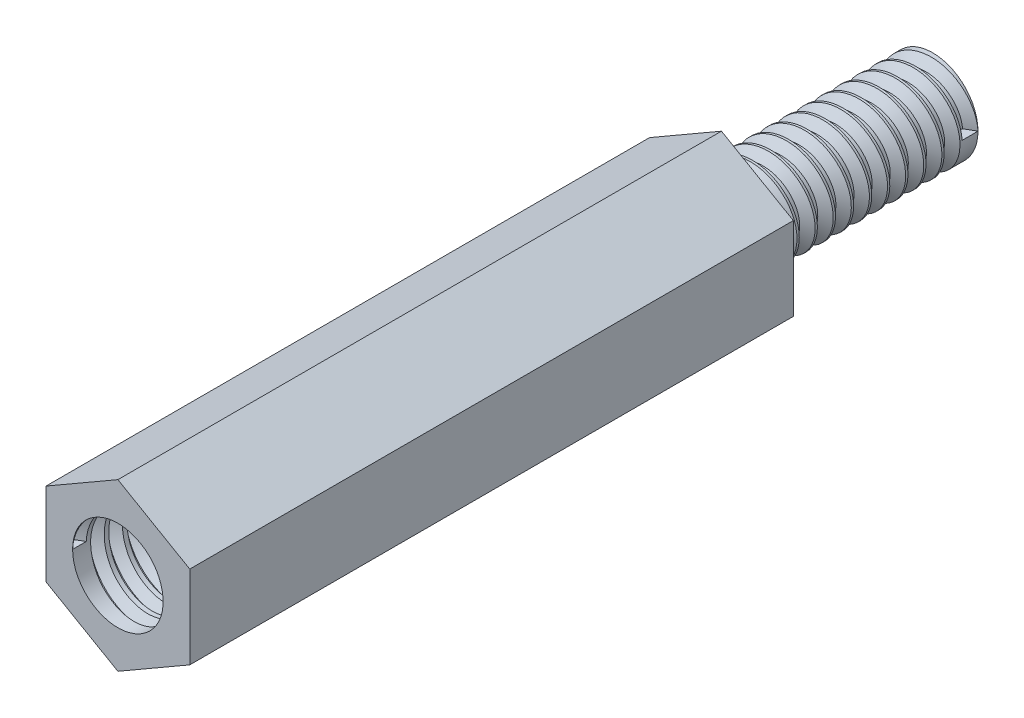
SolidWorks part; units mm, degrees
ref_plane "Front Plane" through (0, 0, 0) normal (0, 0, 1) x (1, 0, 0)
ref_plane "Top Plane" through (0, 0, 0) normal (0, 1, 0) x (1, 0, 0)
ref_plane "Right Plane" through (0, 0, 0) normal (1, 0, 0) x (0, 0, -1)
sketch "Sketch1" plane through (0, 0, 0) normal (0, 0, 1) x (1, 0, 0)
  line L1 (-2.3816, -1.375) -> (0, -2.75)
  line L2 (0, -2.75) -> (2.3816, -1.375)
  line L3 (2.3816, -1.375) -> (2.3816, 1.375)
  line L4 (2.3816, 1.375) -> (0, 2.75)
  line L5 (0, 2.75) -> (-2.3816, 1.375)
  line L6 (-2.3816, 1.375) -> (-2.3816, -1.375)
  circle A0 centre (0, 0) radius 2.3816 construction
  dimension "D1" = 5.5
extrude "Boss-Extrude1" add sketch "Sketch1" along normal blind 20
sketch "Sketch2" plane through (0, 0, 20) normal (0, 0, 1) x (1, 0, 0)
  circle A0 centre (0, 0) radius 1.5
  dimension "D1" = 3
extrude "Cut-Extrude1" cut sketch "Sketch2" against normal blind 7
sketch "Sketch3" plane through (0, 0, 0) normal (0, 0, -1) x (-1, 0, 0)
  circle A0 centre (0, 0) radius 1.5
  dimension "D1" = 3
extrude "Boss-Extrude2" add sketch "Sketch3" along normal blind 7
thread "Thread1" pitch 0.6 method cut profile "Thread Profile1" start angle 0, offset 0, length 0, pitch 0.6, diameter 3
ref_plane "Plane1" through (1.5, 0, -7) normal (0, -1, 0) x (1, 0, 0)
sketch "Thread Profile1" plane through (1.5, 0, -7) normal (0, -1, 0) x (1, 0, 0)
  line L0 (0, 0) -> (0, 0.6) construction
  line L11 (0, 0) -> (0, 0.525)
  line L12 (0, 0.525) -> (-0.3248, 0.3375)
  line L13 (-0.3248, 0.3375) -> (-0.3248, 0.1875)
  line L15 (-0.3248, 0.1875) -> (0, 0)
  line L17 (-0.3248, 0.2625) -> (0, 0.2625) construction
  point P2 (0, 0)
  dimension "Pitch" = 0.6
  dimension "Profile_Angle" = 60
  dimension "Profile_Land" = 0.15
  dimension "Profile_Height" = 0.3248
thread "Thread2" pitch 0.6 method cut profile "Thread Profile2" start angle 0, offset 0, length 0, pitch 0.6, diameter 3
ref_plane "Plane2" through (-1.5, 0, 20) normal (0, -1, 0) x (-1, 0, 0)
sketch "Thread Profile2" plane through (-1.5, 0, 20) normal (0, -1, 0) x (-1, 0, 0)
  line L0 (0, 0) -> (0, 0.6) construction
  line L1 (0, 0) -> (0.3248, 0.1875)
  line L2 (0.3248, 0.1875) -> (0.3248, 0.2625)
  line L3 (0.3248, 0.2625) -> (0, 0.45)
  line L4 (0.3248, 0.225) -> (0, 0.225) construction
  line L11 (0, 0) -> (0, 0.45)
  point P2 (0, 0)
  dimension "Pitch" = 0.6
  dimension "Profile_Angle" = 60
  dimension "Profile_Land" = 0.075
  dimension "Profile_Height" = 0.3248
